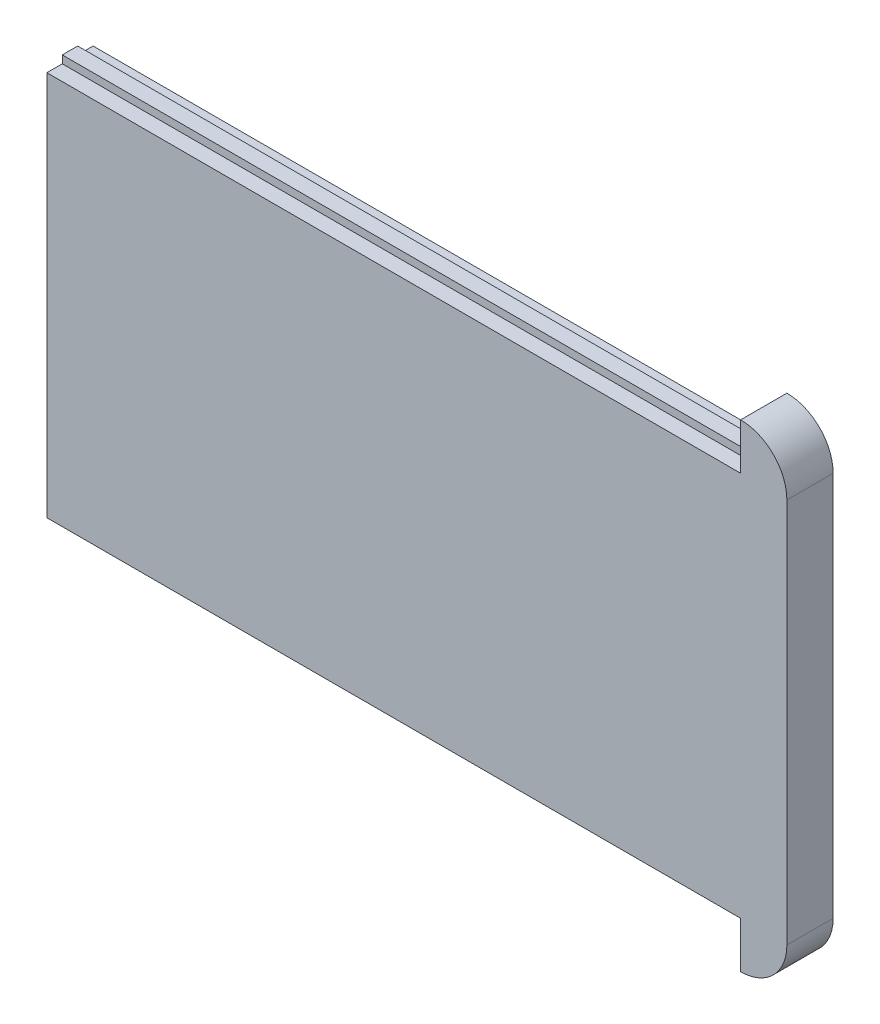
SolidWorks part; units mm, degrees
ref_plane "Front Plane" through (0, 0, 0) normal (0, 0, 1) x (1, 0, 0)
ref_plane "Top Plane" through (0, 0, 0) normal (0, 1, 0) x (1, 0, 0)
ref_plane "Right Plane" through (0, 0, 0) normal (1, 0, 0) x (0, 0, -1)
sketch "Sketch1" plane through (0, 0, 0) normal (0, 0, 1) x (1, 0, 0)
  line L1 (-22.5, 12.5) -> (22.5, 12.5)
  line L2 (-22.5, 12.5) -> (-22.5, -12.5)
  line L3 (-22.5, -12.5) -> (22.5, -12.5)
  line L4 (22.5, 12.5) -> (22.5, -12.5)
  line L5 (-22.5, 12.5) -> (22.5, -12.5) construction
  line L6 (-22.5, -12.5) -> (22.5, 12.5) construction
  point P0 (0, 0)
  dimension "D1" = 25
  dimension "D2" = 45
extrude "Boss-Extrude1" add sketch "Sketch1" along normal blind 3
sketch "Sketch2" plane through (22.5, 0, 0) normal (1, 0, 0) x (0, 0, -1)
  line L0 (-3, -12.5) -> (-3, -15.5)
  line L1 (-3, -15.5) -> (0, -15.5)
  line L2 (0, -15.5) -> (0, -12.5)
  line L3 (-3, -12.5) -> (0, -12.5)
  line L4 (-3, 12.5) -> (0, 12.5)
  line L5 (0, 12.5) -> (0, 15.5)
  line L6 (0, 15.5) -> (-3, 15.5)
  line L7 (-3, 15.5) -> (-3, 12.5)
  dimension "D1" = 3
extrude "Boss-Extrude2" add sketch "Sketch2" against normal blind 3
sketch "Sketch3" plane through (19.5, 0, 0) normal (-1, 0, 0) x (0, 0, 1)
  line L0 (0, -12.5) -> (1, -12.5)
  line L1 (0, -12.5) -> (3, -12.5) construction
  line L2 (1, -12.5) -> (1, -13)
  line L3 (1, -13) -> (2, -13)
  line L4 (2, -13) -> (2, -12.5)
  line L5 (2, -12.5) -> (1, -12.5)
  line L6 (0, 0) -> (4.979, 0) construction
  line L7 (2, 12.5) -> (1, 12.5)
  line L8 (2, 13) -> (2, 12.5)
  line L9 (1, 13) -> (2, 13)
  line L10 (1, 12.5) -> (1, 13)
  line L11 (0, 12.5) -> (1, 12.5)
  line M2 (3, -12.5) -> (0, -12.5)
extrude "Boss-Extrude3" add sketch "Sketch3" along normal blind 45 contours L3 L4 L2 M2 | L10 L7 L8 L9 region at (19.5, -12.75, 1.5) region at (19.5, 12.75, 1.5)
sketch "Sketch4" plane through (-22.5, 0, 0) normal (-1, 0, 0) x (0, 0, 1)
  line L0 (0, 12.5) -> (3, 12.5)
  line L1 (3, 12.5) -> (3, -12.5)
  line L2 (0, 12.5) -> (0, -12.5)
  line L3 (0, -12.5) -> (3, -12.5)
extrude "Boss-Extrude4" add sketch "Sketch4" along normal blind 3
fillet "Fillet1" radius 3 2 edges at (22.5, 15.5, 1.5) (22.5, -15.5, 1.5)
